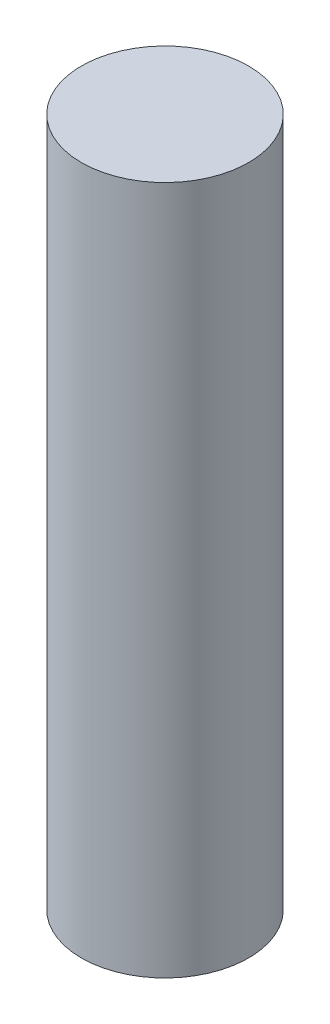
SolidWorks part; units mm, degrees
ref_plane "Front Plane" through (0, 0, 0) normal (0, 0, 1) x (1, 0, 0)
ref_plane "Top Plane" through (0, 0, 0) normal (0, 1, 0) x (1, 0, 0)
ref_plane "Right Plane" through (0, 0, 0) normal (1, 0, 0) x (0, 0, -1)
sketch "Sketch1" plane through (0, 0, 0) normal (0, 1, 0) x (1, 0, 0)
  circle A0 centre (0, 0) radius 8.5
  dimension "D1" = 17
extrude "Boss-Extrude1" add sketch "Sketch1" along normal blind 70
